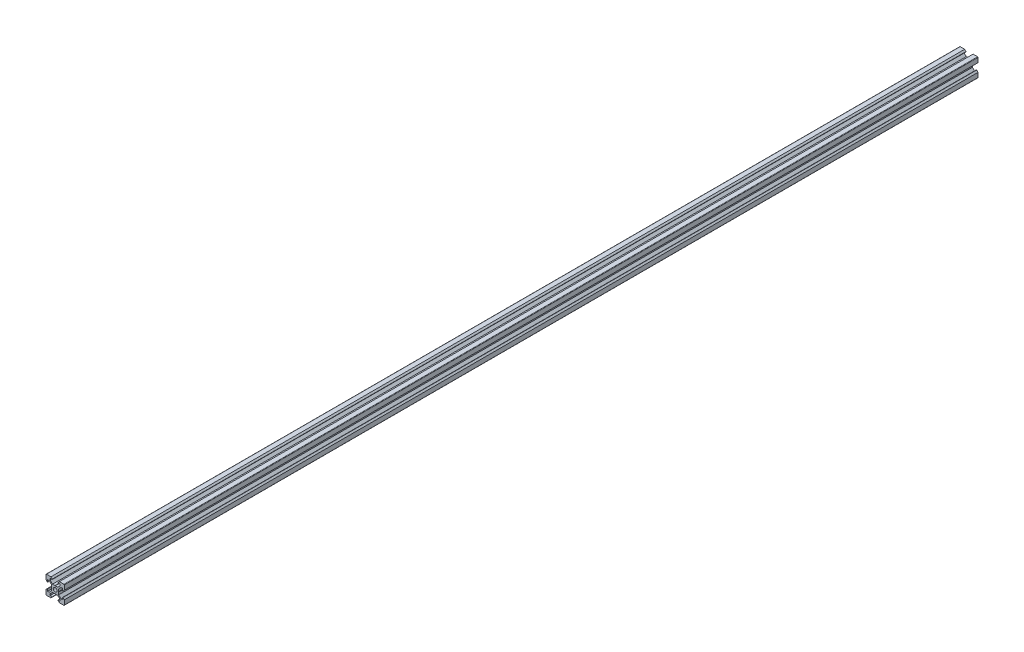
SolidWorks part; units mm, degrees
material "6061-T6 (SS)"
ref_plane "Front Plane" through (0, 0, 0) normal (0, 0, 1) x (1, 0, 0)
ref_plane "Top Plane" through (0, 0, 0) normal (0, 1, 0) x (1, 0, 0)
ref_plane "Right Plane" through (0, 0, 0) normal (1, 0, 0) x (0, 0, -1)
sketch "Sketch1" plane through (0, 0, 0) normal (0, 0, 1) x (1, 0, 0)
  line L1 (9.5, -10) -> (-9.5, -10)
  line L2 (10, -9.5) -> (10, 9.5)
  line L3 (9.5, 10) -> (-9.5, 10)
  line L4 (-10, -9.5) -> (-10, 9.5)
  line L5 (10, -10) -> (-10, 10) construction
  line L6 (10, 10) -> (-10, -10) construction
  circle A0 centre (0, 0) radius 2.1
  arc A1 (-9.5, 10) -> (-10, 9.5) centre (-9.5, 9.5) ccw
  arc A2 (10, 9.5) -> (9.5, 10) centre (9.5, 9.5) ccw
  arc A3 (9.5, -10) -> (10, -9.5) centre (9.5, -9.5) ccw
  arc A4 (-9.5, -10) -> (-10, -9.5) centre (-9.5, -9.5) cw
  point P0 (0, 0)
  line B0 (0, 0) -> (0, 10) construction
  line B1 (0, 3.69) -> (-0.21, 3.9)
  line B2 (-0.21, 3.9) -> (-2.8393, 3.9)
  line B3 (-2.8393, 3.9) -> (-5.5, 6.5607)
  line B4 (-5.5, 6.5607) -> (-5.5, 8.2)
  line B5 (-5.5, 8.2) -> (-3.125, 8.2)
  line B6 (-3.125, 8.2) -> (-3.125, 8.545)
  line B7 (-3.125, 8.545) -> (-4.58, 10)
  line B8 (-4.58, 10) -> (4.58, 10)
  line B9 (0, 0) -> (-5.9132, 5.9132) construction
  line B10 (3.125, 8.545) -> (4.58, 10)
  line B11 (3.125, 8.2) -> (3.125, 8.545)
  line B12 (5.5, 8.2) -> (3.125, 8.2)
  line B13 (5.5, 6.5607) -> (5.5, 8.2)
  line B14 (2.8393, 3.9) -> (5.5, 6.5607)
  line B15 (0.21, 3.9) -> (2.8393, 3.9)
  line B16 (0, 3.69) -> (0.21, 3.9)
  line B17 (0, 0) -> (-10, 0) construction
  line B18 (-3.69, 0) -> (-3.9, -0.21)
  line B19 (-3.9, -0.21) -> (-3.9, -2.8393)
  line B20 (-3.9, -2.8393) -> (-6.5607, -5.5)
  line B21 (-6.5607, -5.5) -> (-8.2, -5.5)
  line B22 (-8.2, -5.5) -> (-8.2, -3.125)
  line B23 (-8.2, -3.125) -> (-8.545, -3.125)
  line B24 (-8.545, -3.125) -> (-10, -4.58)
  line B25 (-10, -4.58) -> (-10, 4.58)
  line B26 (0, 0) -> (-5.9132, -5.9132) construction
  line B27 (-8.545, 3.125) -> (-10, 4.58)
  line B28 (-8.2, 3.125) -> (-8.545, 3.125)
  line B29 (-8.2, 5.5) -> (-8.2, 3.125)
  line B30 (-6.5607, 5.5) -> (-8.2, 5.5)
  line B31 (-3.9, 2.8393) -> (-6.5607, 5.5)
  line B32 (-3.9, 0.21) -> (-3.9, 2.8393)
  line B33 (-3.69, 0) -> (-3.9, 0.21)
  line B34 (0, 0) -> (0, -10) construction
  line B35 (0, -3.69) -> (0.21, -3.9)
  line B36 (0.21, -3.9) -> (2.8393, -3.9)
  line B37 (2.8393, -3.9) -> (5.5, -6.5607)
  line B38 (5.5, -6.5607) -> (5.5, -8.2)
  line B39 (5.5, -8.2) -> (3.125, -8.2)
  line B40 (3.125, -8.2) -> (3.125, -8.545)
  line B41 (3.125, -8.545) -> (4.58, -10)
  line B42 (4.58, -10) -> (-4.58, -10)
  line B43 (0, 0) -> (5.9132, -5.9132) construction
  line B44 (-3.125, -8.545) -> (-4.58, -10)
  line B45 (-3.125, -8.2) -> (-3.125, -8.545)
  line B46 (-5.5, -8.2) -> (-3.125, -8.2)
  line B47 (-5.5, -6.5607) -> (-5.5, -8.2)
  line B48 (-2.8393, -3.9) -> (-5.5, -6.5607)
  line B49 (-0.21, -3.9) -> (-2.8393, -3.9)
  line B50 (0, -3.69) -> (-0.21, -3.9)
  line B51 (0, 0) -> (10, 0) construction
  line B52 (3.69, 0) -> (3.9, 0.21)
  line B53 (3.9, 0.21) -> (3.9, 2.8393)
  line B54 (3.9, 2.8393) -> (6.5607, 5.5)
  line B55 (6.5607, 5.5) -> (8.2, 5.5)
  line B56 (8.2, 5.5) -> (8.2, 3.125)
  line B57 (8.2, 3.125) -> (8.545, 3.125)
  line B58 (8.545, 3.125) -> (10, 4.58)
  line B59 (10, 4.58) -> (10, -4.58)
  line B60 (0, 0) -> (5.9132, 5.9132) construction
  line B61 (8.545, -3.125) -> (10, -4.58)
  line B62 (8.2, -3.125) -> (8.545, -3.125)
  line B63 (8.2, -5.5) -> (8.2, -3.125)
  line B64 (6.5607, -5.5) -> (8.2, -5.5)
  line B65 (3.9, -2.8393) -> (6.5607, -5.5)
  line B66 (3.9, -0.21) -> (3.9, -2.8393)
  line B67 (3.69, 0) -> (3.9, -0.21)
  dimension "D1" = 4.2
  dimension "D3" = 0.5
  dimension "D2" = 20
sketch_block_instance "V Slot 1-4"
sketch_block "V Slot 1" parameters "D1"=10, "D2"=11, "D3"=4.3, "D4"=1.8, "D5"=0.21, "D6"=45, "D7"=9.16, "D8"=1.5, "D9"=6.25
sketch_block_instance "V Slot 1-5"
sketch_block_instance "V Slot 1-6"
sketch_block_instance "V Slot 1-7"
extrude "Boss-Extrude1" add sketch "Sketch1" along normal mid plane 1000 contours B67 B52 B53 B54 B55 B56 B57 B58 L2 A2 L3 B10 B11 B12 B13 B14 B15 B16 B1 B2 B3 B4 B5 B6 B7 A1 L4 B27 B28 B29 B30 B31 B32 B33 B18 B19 B20 B21 B22 B23 B24 A4 L1 B44 B45 B46 B47 B48 B49 region at (7.04, -9.7172, 0)
